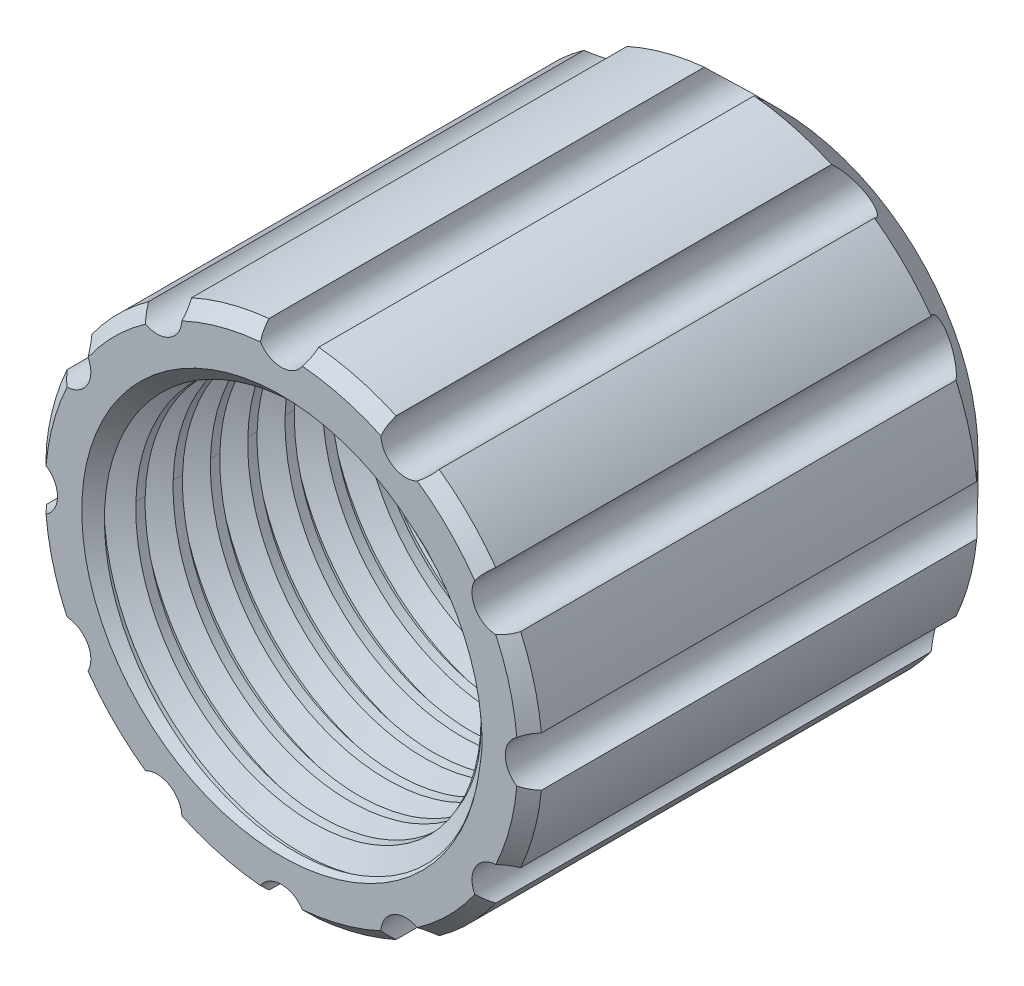
SolidWorks part; units mm, degrees
ref_plane "Front" through (0, 0, 0) normal (0, 0, 1) x (1, 0, 0)
ref_plane "Top" through (0, 0, 0) normal (0, 1, 0) x (1, 0, 0)
ref_plane "Right" through (0, 0, 0) normal (1, 0, 0) x (0, 0, -1)
other "Configuration Table"
sketch "Sketch1" plane through (0, 0, 0) normal (0, 0, 1) x (1, 0, 0)
  circle A0 centre (0, 0) radius 10
  dimension "D1" = 20
extrude "Boss-Extrude1" add sketch "Sketch1" along normal blind 20
sketch "Sketch2" plane through (0, 0, 20) normal (0, 0, 1) x (1, 0, 0)
  circle A0 centre (0, 0) radius 7.75
  dimension "D1" = 15.5
chamfer "Chamfer1" distance 2 angle 45 1 edges at (10, 0, 0)
chamfer "Chamfer3" distance 0.5 angle 45 1 edges at (10, 0, 20)
sketch "Sketch6" plane through (0, 0, 20) normal (0, 0, 1) x (1, 0, 0)
  circle A0 centre (0, 10) radius 1
  circle A1 centre (0, 0) radius 10 construction
  circle A2 centre (5, 8.6603) radius 1
  circle A3 centre (8.6603, 5) radius 1
  circle A4 centre (10, 0) radius 1
  circle A5 centre (8.6603, -5) radius 1
  circle A6 centre (5, -8.6603) radius 1
  circle A7 centre (0, -10) radius 1
  circle A8 centre (-5, -8.6603) radius 1
  circle A9 centre (-8.6603, -5) radius 1
  circle A10 centre (-10, 0) radius 1
  circle A11 centre (-8.6603, 5) radius 1
  circle A12 centre (-5, 8.6603) radius 1
  point P29 (0, 0)
  dimension "D1" = 2
  dimension "D2" = 12
extrude "Cut-Extrude2" cut sketch "Sketch6" against normal through all
hole_wizard "M16x1.5 Tapped Hole1" positions "Sketch7" profile "Sketch9" tap size "M16x1.5" standard "ANSI Metric" end condition through all
sketch "Sketch7" plane through (0, 0, 20) normal (0, 0, 1) x (1, 0, 0)
  point P0 (0, 0)
sketch "Sketch9" plane through (0, 0, 20) normal (1, 0, 0) x (0, -1, 0)
  line L0 (0, 0) -> (0, 20)
  line L1 (0, 20) -> (7.25, 20)
  line L2 (7.25, 20) -> (7.25, 0.775)
  line L3 (7.25, 0.775) -> (8.025, 0)
  line L5 (8.025, 0) -> (0, 0)
  line L6 (-7.25, 0.775) -> (-8.025, 0) construction
  line L11 (0, -6.35) -> (0, 107.95) construction
  dimension "Thru Tap Drill Dia." = 14.5
  dimension "Thru Tap Drill Depth" = 20
  dimension "Near C'Sink Dia." = 16.05
  dimension "Near C'Sink Angle" = 90
thread "Thread1" pitch 1.5 method cut profile "Thread Profile1" start angle 0, offset 2, length 15, pitch 1.5, diameter 14.5
ref_plane "Plane1" through (-7.25, 0, 21.225) normal (0, -1, 0) x (-1, 0, 0)
sketch "Thread Profile1" plane through (-7.25, 0, 21.225) normal (0, -1, 0) x (-1, 0, 0)
  line L0 (0, 0) -> (0, 1.5) construction
  line L1 (0, 0) -> (0.8119, 0.4687)
  line L2 (0.8119, 0.4687) -> (0.8119, 0.6562)
  line L3 (0.8119, 0.6562) -> (0, 1.125)
  line L4 (0.8119, 0.5625) -> (0, 0.5625) construction
  line L11 (0, 0) -> (0, 1.125)
  point P2 (0, 0)
  dimension "Pitch" = 1.5
  dimension "Profile_Angle" = 60
  dimension "Profile_Land" = 0.1875
  dimension "Profile_Height" = 0.8119
sketch "Sketch13" plane through (0, 0, 0) normal (0, 0, -1) x (-1, 0, 0)
  circle A0 centre (0, 0) radius 7.25
extrude "Boss-Extrude2" add sketch "Sketch13" against normal blind 3
